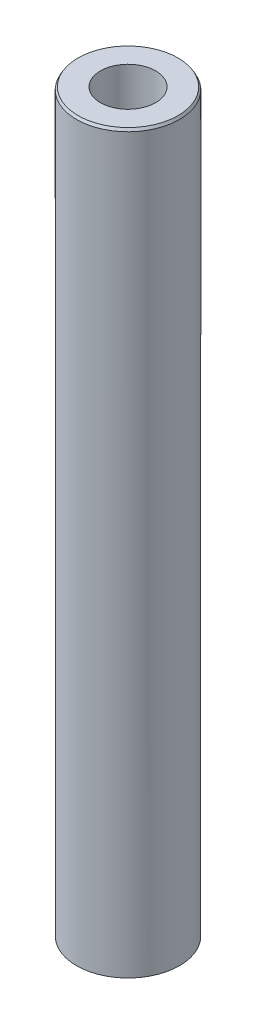
SolidWorks part; units mm, degrees
ref_plane "Front Plane" through (0, 0, 0) normal (0, 0, 1) x (1, 0, 0)
ref_plane "Top Plane" through (0, 0, 0) normal (0, 1, 0) x (1, 0, 0)
ref_plane "Right Plane" through (0, 0, 0) normal (1, 0, 0) x (0, 0, -1)
sketch "Sketch1" plane through (0, 0, 0) normal (0, 1, 0) x (1, 0, 0)
  circle A0 centre (0, 0) radius 37.5
  dimension "SHAFT_OD" = 75
extrude "Boss-Extrude1" add sketch "Sketch1" along normal blind 536.8107
sketch "Sketch2" plane through (0, 0, 0) normal (0, 1, 0) x (1, 0, 0)
  circle A0 centre (0, 0) radius 20.1042
  dimension "BORE_D" = 40.2084
extrude "Cut-Extrude1" cut sketch "Sketch2" along normal through all
chamfer "Chamfer1" distance 1.8908 angle 30 2 edges at (0, 536.8107, 37.5) (0, 0, 37.5) first distance on face at (0, 536.8107, 37.5) first distance on face at (0, 0, 20.1042)
